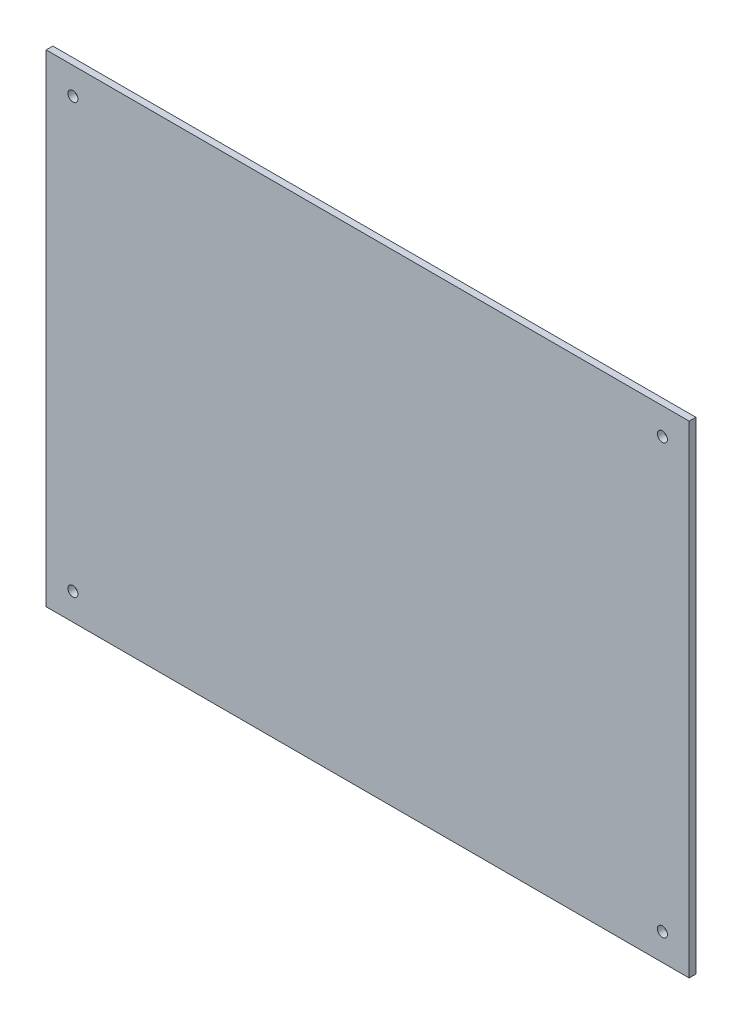
SolidWorks part; units mm, degrees
ref_plane "Front Plane" through (0, 0, 0) normal (0, 0, 1) x (1, 0, 0)
ref_plane "Top Plane" through (0, 0, 0) normal (0, 1, 0) x (1, 0, 0)
ref_plane "Right Plane" through (0, 0, 0) normal (1, 0, 0) x (0, 0, -1)
sketch "Sketch1" plane through (0, 0, 0) normal (0, 0, 1) x (1, 0, 0)
  line L0 (-139.7, 114.3) -> (-139.7, -114.3) construction
  line L1 (152.4, -114.3) -> (-152.4, -114.3)
  line L2 (152.4, -114.3) -> (152.4, 114.3)
  line L3 (152.4, 114.3) -> (-152.4, 114.3)
  line L4 (-152.4, -114.3) -> (-152.4, 114.3)
  line L5 (152.4, -114.3) -> (-152.4, 114.3) construction
  line L6 (152.4, 114.3) -> (-152.4, -114.3) construction
  line L7 (-152.4, 101.6) -> (152.4, 101.6) construction
  line L8 (139.7, 114.3) -> (139.7, -114.3) construction
  line L9 (-152.4, -101.6) -> (152.4, -101.6) construction
  circle A0 centre (139.7, 101.6) radius 2.3813
  circle A1 centre (-139.7, 101.6) radius 2.3813
  circle A2 centre (-139.7, -101.6) radius 2.3813
  circle A3 centre (139.7, -101.6) radius 2.3813
  point P0 (0, 0)
  point P14 (-139.7, 101.6)
  point P16 (-139.7, -101.6)
  point P17 (139.7, -101.6)
  point P18 (139.7, 101.6)
  dimension "D7" = 4.7625
  dimension "D1" = 304.8
  dimension "D2" = 228.6
  dimension "D3" = 12.7
  dimension "D4" = 12.7
  dimension "D5" = 12.7
  dimension "D6" = 12.7
extrude "Boss-Extrude1" add sketch "Sketch1" along normal blind 3.175
